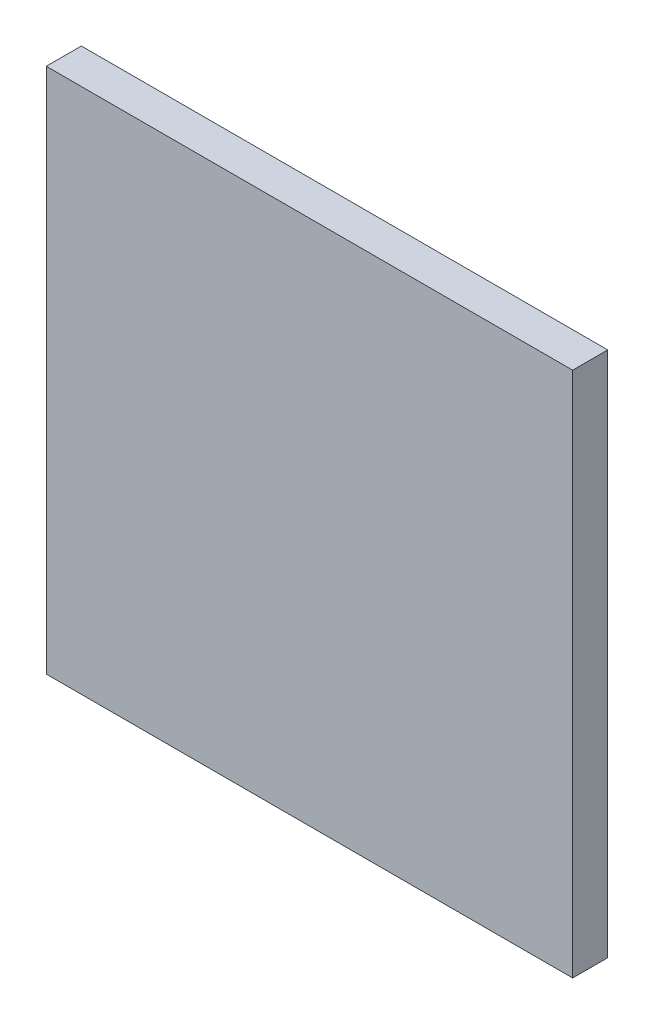
SolidWorks part; units mm, degrees
ref_plane "前视基准面" through (0, 0, 0) normal (0, 0, 1) x (1, 0, 0)
ref_plane "上视基准面" through (0, 0, 0) normal (0, 1, 0) x (1, 0, 0)
ref_plane "右视基准面" through (0, 0, 0) normal (1, 0, 0) x (0, 0, -1)
sketch "草图2" plane through (0, 0, 0) normal (0, 0, 1) x (1, 0, 0)
  line L1 (-75, -75) -> (75, -75)
  line L2 (-75, -75) -> (-75, 75)
  line L3 (-75, 75) -> (75, 75)
  line L4 (75, -75) -> (75, 75)
  line L5 (-75, -75) -> (75, 75) construction
  line L6 (-75, 75) -> (75, -75) construction
  point P0 (0, 0)
  dimension "D1" = 150
extrude "凸台-拉伸1" add sketch "草图2" along normal blind 10
